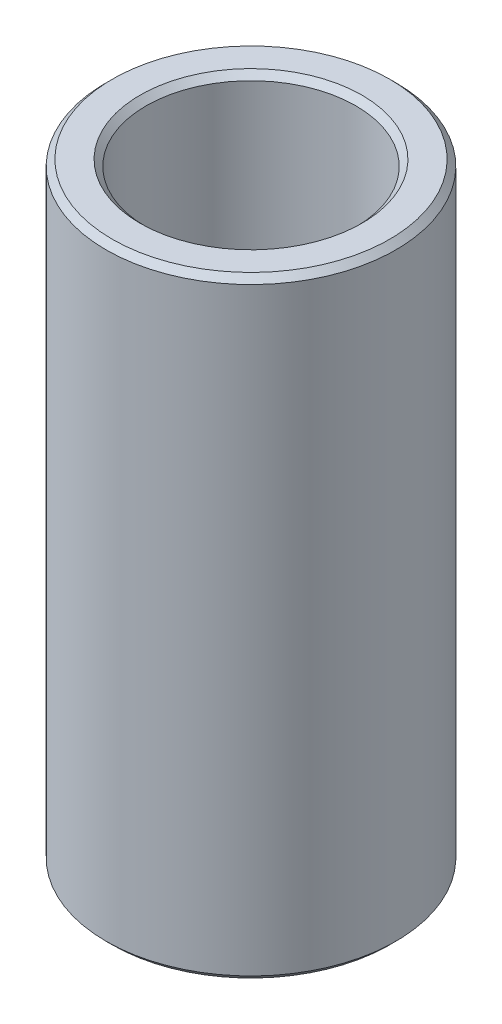
SolidWorks part; units mm, degrees
ref_plane "Front Plane" through (0, 0, 0) normal (0, 0, 1) x (1, 0, 0)
ref_plane "Top Plane" through (0, 0, 0) normal (0, 1, 0) x (1, 0, 0)
ref_plane "Right Plane" through (0, 0, 0) normal (1, 0, 0) x (0, 0, -1)
sketch "Sketch1" plane through (0, 0, 0) normal (0, 1, 0) x (1, 0, 0)
  circle A0 centre (0, 0) radius 42.5
  dimension "SLEEVE_OD" = 85
extrude "Boss-Extrude1" add sketch "Sketch1" along normal blind 179.3097
sketch "Sketch2" plane through (0, 0, 0) normal (0, 1, 0) x (1, 0, 0)
  circle A0 centre (0, 0) radius 30.7638
  dimension "BORE_D" = 61.5276
extrude "Cut-Extrude1" cut sketch "Sketch2" along normal through all
chamfer "Chamfer1" distance 1.8053 angle 45 4 edges at (0, 179.3097, 30.7638) (0, 0, 30.7638) (0, 0, 42.5) (0, 179.3097, 42.5)
